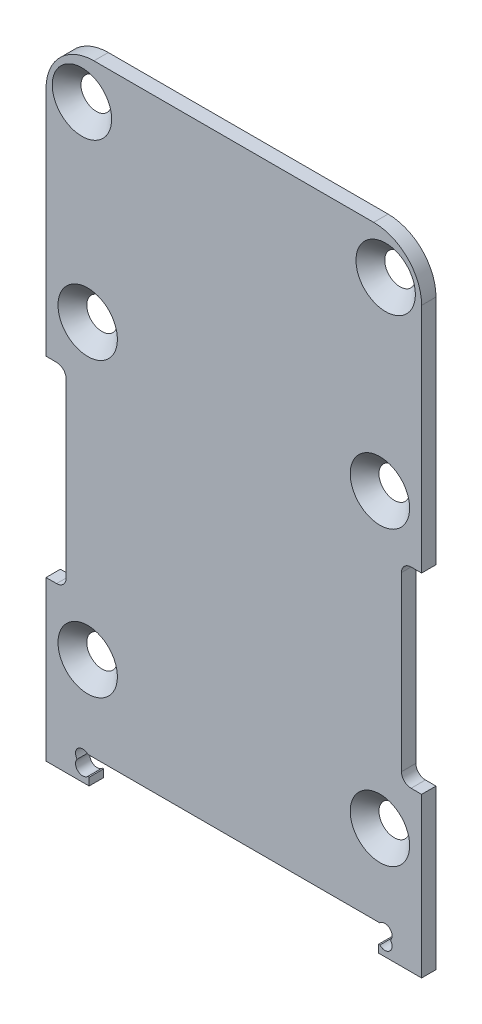
SolidWorks part; units mm, degrees
ref_plane "Front Plane" through (0, 0, 0) normal (0, 0, 1) x (1, 0, 0)
ref_plane "Top Plane" through (0, 0, 0) normal (0, 1, 0) x (1, 0, 0)
ref_plane "Right Plane" through (0, 0, 0) normal (1, 0, 0) x (0, 0, -1)
sketch "Sketch1" plane through (0, 0, 0) normal (0, 0, 1) x (1, 0, 0)
  line L1 (-19.6, 39.2) -> (19.6, 39.2)
  line L2 (-19.6, 39.2) -> (-19.6, -26.6)
  line L3 (-19.6, -26.6) -> (19.6, -26.6)
  line L4 (19.6, 39.2) -> (19.6, -26.6)
  line L11 (15.1, -26.6) -> (15.1, -25.8)
  line L12 (15.1, -25.8) -> (16.3, -25.8)
  line L13 (16.3, -23.8) -> (16.3, -25.8)
  line L14 (-16.3, -23.8) -> (16.3, -23.8)
  line L15 (-16.3, -23.8) -> (-16.3, -25.8)
  line L16 (-16.3, -25.8) -> (-15.1, -25.8)
  line L17 (-15.1, -26.6) -> (-15.1, -25.8)
  dimension "D1" = 65.8
  dimension "D2" = 39.2
extrude "Base" add sketch "Sketch1" along normal blind 1.5 contours L3 L17 L16 L15 L14 L13 L12 L11 L4 L1 L2 region at (0, 7.4297, 0)
sketch "Sketch2" plane through (0, 0, 1.5) normal (0, 0, 1) x (1, 0, 0)
  line L0 (0, 34.85) -> (0, -15.25) construction
  line L1 (15.25, 34.85) -> (-15.25, 34.85) construction
  line L2 (15.25, -15.25) -> (-15.25, -15.25) construction
  line L3 (-15.25, 0) -> (15.25, 0) construction
  line L4 (-15.25, -15.25) -> (-15.25, 34.85) construction
  line L5 (15.25, -15.25) -> (15.25, 34.85) construction
  circle A0 centre (-15.25, 15.25) radius 1.6
  circle A1 centre (-15.85, 34.85) radius 1.6
  circle A2 centre (15.85, 34.85) radius 1.6
  circle A3 centre (15.25, 15.25) radius 1.6
  circle A4 centre (15.25, -15.25) radius 1.6
  circle A5 centre (-15.25, -15.25) radius 1.6
  circle A6 centre (-15.85, 34.85) radius 1.6 construction
  circle A7 centre (15.85, 34.85) radius 1.6 construction
  dimension "D1" = 3.2
sketch "Sketch3" plane through (0, 0, 1.5) normal (0, 0, 1) x (1, 0, 0)
  line L0 (-17.5, 43.3) -> (-17.5, -30.7) construction
  line L1 (-17.5, -10) -> (-19.6, -10)
  line L2 (-17.5, -10) -> (-17.5, 10)
  line L3 (-17.5, 10) -> (-19.6, 10)
  line L4 (-19.6, -10) -> (-19.6, 10)
  line L5 (-17.5, -10) -> (-19.6, 10) construction
  line L6 (-17.5, 10) -> (-19.6, -10) construction
  line L7 (-19.6, 39.2) -> (-19.6, -26.6) construction
  line L8 (0, 0) -> (-19.6, 0) construction
  point P4 (-18.55, 0)
extrude "Battery strap cut" cut sketch "Sketch3" against normal up to next
fillet "Battery strap fillet" radius 1 2 edges at (-17.5, -10, 0.75) (-17.5, 10, 0.75)
mirror "Battery strap other side" about plane through (0, 0, 0) normal (1, 0, 0) of "Battery strap cut", "Battery strap fillet"
fillet "Fillet2" radius 5 2 edges at (-19.6, 39.2, 0.75) (19.6, 39.2, 0.75)
extrude "Hole cut" cut sketch "Sketch2" against normal up to next
chamfer "Bolt head chamber" distance 1.5 angle 45 6 edges at (-13.65, 15.25, 1.5) (-16.85, -15.25, 1.5) (16.85, -15.25, 1.5) (-14.25, 34.85, 1.5) (17.45, 34.85, 1.5) (13.65, 15.25, 1.5)
sketch "Sketch4" plane through (0, 0, 1.5) normal (0, 0, 1) x (1, 0, 0)
  line L0 (-15.7697, -24.3303) -> (-16.3, -23.8) construction
  line L1 (-16.3, -23.8) -> (-16.3, -25.8) construction
  line L2 (-16.3, -24.8) -> (-15.1139, -24.8) construction
  line L3 (0, -23.8) -> (0, -26.7588) construction
  line L4 (-16.3, -23.8) -> (16.3, -23.8) construction
  circle A0 centre (-15.7697, -24.3303) radius 0.75
  circle A1 centre (-15.7697, -25.2697) radius 0.75
  circle A2 centre (15.7697, -25.2697) radius 0.75
  circle A3 centre (15.7697, -24.3303) radius 0.75
  dimension "D2" = 1.5
  dimension "D1" = 45
extrude "Milling holes" cut sketch "Sketch4" against normal blind 10 contours A0 | A1 | A2 | A3
